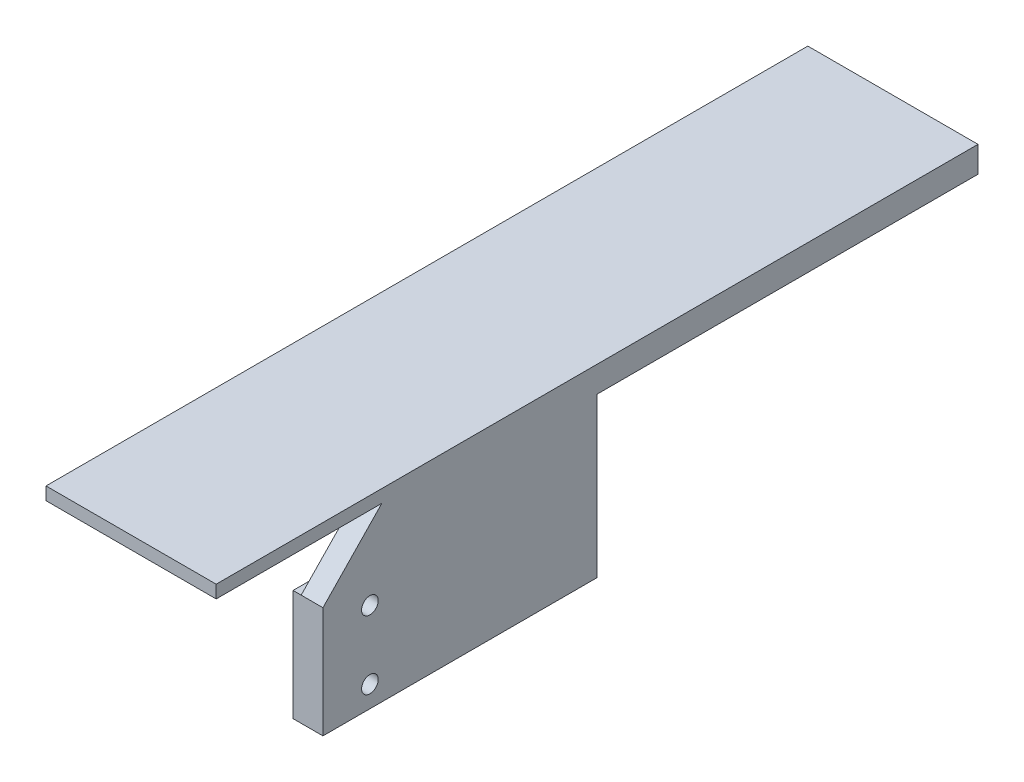
SolidWorks part; units mm, degrees
ref_plane "Front Plane" through (0, 0, 0) normal (0, 0, 1) x (1, 0, 0)
ref_plane "Top Plane" through (0, 0, 0) normal (0, 1, 0) x (1, 0, 0)
ref_plane "Right Plane" through (0, 0, 0) normal (1, 0, 0) x (0, 0, -1)
ref_plane "PY -20.700" through (0, -20.7, 0) normal (0, 1, 0) x (1, 0, 0)
sketch "leg and pad sketch" plane through (0, -20.7, 0) normal (0, 1, 0) x (1, 0, 0)
  line L0 (-0.5513, 30.3327) -> (-0.3673, 30.8194)
  line L1 (-0.3673, 30.8194) -> (-0.028, 31.2139)
  line L2 (-0.028, 31.2139) -> (0.4256, 31.4688)
  line L3 (0.4256, 31.4688) -> (0.939, 31.5534)
  line L4 (0.939, 31.5534) -> (1.4504, 31.4576)
  line L5 (1.4504, 31.4576) -> (1.8983, 31.1928)
  line L6 (1.8983, 31.1928) -> (2.2288, 30.7909)
  line L7 (2.2288, 30.7909) -> (2.4021, 30.3003)
  line L8 (2.4021, 30.3003) -> (2.3973, 29.78)
  line L9 (2.3973, 29.78) -> (2.2152, 29.2926)
  line L10 (2.2152, 29.2926) -> (1.8775, 28.8968)
  line L11 (1.8775, 28.8968) -> (1.4248, 28.6402)
  line L12 (1.4248, 28.6402) -> (0.9118, 28.5536)
  line L13 (0.9118, 28.5536) -> (0.4, 28.6475)
  line L14 (0.4, 28.6475) -> (0.4, -9.98)
  line L15 (0.4, -9.98) -> (1.92, -11.5)
  line L16 (1.92, -11.5) -> (1.92, -31.37)
  line L17 (1.92, -31.37) -> (8.92, -31.37)
  line L18 (8.92, -31.37) -> (8.92, 32.7926)
  line L19 (8.92, 32.7926) -> (-27.2048, 54.5947)
  line L20 (-27.2048, 54.5947) -> (-30.8218, 48.6015)
  line L21 (-30.8218, 48.6015) -> (-0.5513, 30.3327)
extrude "leg and pad" add sketch "leg and pad sketch" along normal mid plane 26
ref_plane "PX 1.350" through (1.35, 0, 0) normal (1, 0, 0) x (0, 0, -1)
sketch "screw head relief sketch" plane through (1.35, 0, 0) normal (1, 0, 0) x (0, 0, -1)
  line L0 (23.4, -12.7) -> (23.4, -6.7)
  line L1 (23.4, -6.7) -> (9.4, -6.7)
  line L2 (9.4, -6.7) -> (9.4, -12.7)
  line L3 (9.4, -12.7) -> (23.4, -12.7)
extrude "screw head relief" cut sketch "screw head relief sketch" against normal mid plane 4.7
sketch "insert flange relief sketch" plane through (0, -20.7, 0) normal (0, 1, 0) x (1, 0, 0)
  line L0 (-18.3249, 39.8914) -> (-17.0331, 42.0318)
  line L1 (-17.0331, 42.0318) -> (-9.7557, 37.6398)
  line L2 (-9.7557, 37.6398) -> (-11.0475, 35.4994)
  line L3 (-11.0475, 35.4994) -> (-18.3249, 39.8914)
revolve "insert flange relief" cut sketch "insert flange relief sketch" angle 360 about L0
sketch "M6 slot end 1 sketch" plane through (0, -20.7, 0) normal (0, 1, 0) x (1, 0, 0)
  line L0 (-20.8933, 41.4415) -> (-16.243, 49.147)
  line L1 (-16.243, 49.147) -> (-13.2464, 47.3385)
  line L2 (-13.2464, 47.3385) -> (-17.8968, 39.633)
  line L3 (-17.8968, 39.633) -> (-20.8933, 41.4415)
revolve "M6 slot end 1" cut sketch "M6 slot end 1 sketch" angle 360 about L0
sketch "M6 slot end 2 sketch" plane through (0, -20.7, 0) normal (0, 1, 0) x (1, 0, 0)
  line L0 (-15.7564, 38.3413) -> (-11.106, 46.0467)
  line L1 (-11.106, 46.0467) -> (-8.1094, 44.2382)
  line L2 (-8.1094, 44.2382) -> (-12.7598, 36.5328)
  line L3 (-12.7598, 36.5328) -> (-15.7564, 38.3413)
revolve "M6 slot end 2" cut sketch "M6 slot end 2 sketch" angle 360 about L0
sketch "M6 slot middle sketch" plane through (0, -20.7, 0) normal (0, 1, 0) x (1, 0, 0)
  line L0 (-15.7564, 38.3413) -> (-20.8933, 41.4415)
  line L1 (-20.8933, 41.4415) -> (-16.243, 49.147)
  line L2 (-16.243, 49.147) -> (-11.106, 46.0467)
  line L3 (-11.106, 46.0467) -> (-15.7564, 38.3413)
extrude "M6 slot middle" cut sketch "M6 slot middle sketch" against normal mid plane 7
ref_plane "PX 5.420" through (5.42, 0, 0) normal (1, 0, 0) x (0, 0, -1)
sketch "screw holes sketch" plane through (5.42, 0, 0) normal (1, 0, 0) x (0, 0, -1)
  circle A0 centre (-20.375, -28.7) radius 1.95
  circle A1 centre (-20.375, -12.7) radius 1.95
extrude "screw holes" cut sketch "screw holes sketch" against normal mid plane 9
ref_plane "PY -2.100" through (0, -2.1, 0) normal (0, 1, 0) x (1, 0, 0)
sketch "foot leg sketch" plane through (0, -2.1, 0) normal (0, 1, 0) x (1, 0, 0)
  line L0 (2.3, 30.0135) -> (2.3, -9.98)
  line L1 (2.3, -9.98) -> (8.92, -9.98)
  line L2 (8.92, -9.98) -> (8.92, 32.7926)
  line L3 (8.92, 32.7926) -> (-27.2048, 54.5947)
  line L4 (-27.2048, 54.5947) -> (-30.2017, 49.6289)
  line L5 (-30.2017, 49.6289) -> (2.3, 30.0135)
extrude "foot leg" add sketch "foot leg sketch" along normal mid plane 12.2
ref_plane "PY 6.535" through (0, 6.535, 0) normal (0, 1, 0) x (1, 0, 0)
sketch "sole under the housing sketch" plane through (0, 6.535, 0) normal (0, 1, 0) x (1, 0, 0)
  line L0 (-30.9218, 122) -> (8.92, 122)
  line L1 (8.92, 122) -> (8.92, -13.03)
  line L2 (8.92, -13.03) -> (-30.9218, -13.03)
  line L3 (-30.9218, -13.03) -> (-30.9218, 122)
extrude "sole under the housing" add sketch "sole under the housing sketch" along normal mid plane 6.07
ref_plane "PY 8.070" through (0, 8.07, 0) normal (0, 1, 0) x (1, 0, 0)
sketch "sole under the block sketch" plane through (0, 8.07, 0) normal (0, 1, 0) x (1, 0, 0)
  line L0 (-30.9218, -12.53) -> (8.92, -12.53)
  line L1 (8.92, -12.53) -> (8.92, -56.37)
  line L2 (8.92, -56.37) -> (-30.9218, -56.37)
  line L3 (-30.9218, -56.37) -> (-30.9218, -12.53)
extrude "sole under the block" add sketch "sole under the block sketch" along normal mid plane 3
ref_plane "PX 6.370" through (6.37, 0, 0) normal (1, 0, 0) x (0, 0, -1)
sketch "seat gusset sketch" plane through (6.37, 0, 0) normal (1, 0, 0) x (0, 0, -1)
  line L0 (-9.48, -8.2) -> (-31.37, -8.2)
  line L1 (-31.37, -8.2) -> (-31.37, -7.7)
  line L2 (-31.37, -7.7) -> (-17.1, 7.07)
  line L3 (-17.1, 7.07) -> (-9.48, 7.07)
  line L4 (-9.48, 7.07) -> (-9.48, -8.2)
extrude "seat gusset" add sketch "seat gusset sketch" along normal mid plane 5.1
ref_plane "PX -19.922" through (-19.9218, 0, 0) normal (1, 0, 0) x (0, 0, -1)
sketch "tail rib sketch" plane through (-19.9218, 0, 0) normal (1, 0, 0) x (0, 0, -1)
  line L0 (53.1, 4) -> (53.1, -12.5)
  line L1 (53.1, -12.5) -> (57.1, -12.5)
  line L2 (57.1, -12.5) -> (120, 3.5)
  line L3 (120, 3.5) -> (120, 4)
  line L4 (120, 4) -> (53.1, 4)
extrude "tail rib" add sketch "tail rib sketch" along normal mid plane 6
sketch "screw head relief to the end sketch" plane through (1.35, 0, 0) normal (1, 0, 0) x (0, 0, -1)
  line L0 (23.4, -12.7) -> (23.4, 3.3)
  line L1 (23.4, 3.3) -> (9.4, 3.3)
  line L2 (9.4, 3.3) -> (9.4, -12.7)
  line L3 (9.4, -12.7) -> (23.4, -12.7)
extrude "screw head relief to the end" cut sketch "screw head relief to the end sketch" against normal mid plane 4.7
equation "\"diffL\" = 608.8mm"
equation "\"diffW\" = 329.4mm"
equation "\"diffT\" = 2.9mm"
equation "\"chanSlotW\" = 12.9mm"
equation "\"chanSlotDepth\" = 11.13mm"
equation "\"chanFloor\" = 1.57mm"
equation "\"chanLeg\" = 12.7mm"
equation "\"lightL\" = 604.8mm"
equation "\"lightW\" = 330.2mm"
equation "\"lightH\" = 92mm"
equation "\"lightSideFlat\" = 30mm"
equation "\"lightSlopeLen\" = 38.9mm"
equation "\"lightWingDepth\" = 50.1mm"
equation "\"lightWingFlat\" = 90.2mm"
equation "\"lightChanW\" = 99.6mm"
equation "\"lightChanStand\" = 44.1mm"
equation "\"insFlangeD\" = 12.3mm"
equation "\"insFromEnd\" = 20.7mm"
equation "\"insUpSlope\" = 20.8mm"
equation "\"gaugeH\" = 10mm"
equation "\"gaugeStepLen\" = 14mm"
equation "\"gaugeStepW0\" = 13.1mm"
equation "\"gaugeStepDW\" = 0.2mm"
equation "\"gaugeSteps\" = 5mm"
equation "\"gaugeHandleLen\" = 30mm"
equation "\"gaugeHandleW\" = 24mm"
equation "\"gaugeSlot0\" = 3mm"
equation "\"gaugeSlotD\" = 0.1mm"
equation "\"gaugeSlotDepth\" = 8mm"
equation "\"gap\" = 25.4mm"
equation "\"edgeL\" = 1mm"
equation "\"edgeW\" = 0.75mm"
equation "\"proud\" = 1.5mm"
equation "\"seatClr\" = 0.15mm"
equation "\"tongueClrZ\" = 0.1mm"
equation "\"tongueClrX\" = 0.25mm"
equation "\"tongueLen\" = 30mm"
equation "\"armSide\" = 45mm"
equation "\"armEnd\" = 20mm"
equation "\"cornerCham\" = 3mm"
equation "\"brkW\" = 26mm"
equation "\"brkT\" = 7mm"
equation "\"brkSeatClr\" = 0.3mm"
equation "\"brkScrewSpan\" = 16mm"
equation "\"pilotD\" = 2.7mm"
equation "\"pilotDepth\" = 10mm"
equation "\"screwClrD\" = 3.9mm"
equation "\"jogBelow\" = 4mm"
equation "\"padT\" = 7mm"
equation "\"padLen\" = 36mm"
equation "\"m6Clr\" = 7mm"
equation "\"m6Slot\" = 6mm"
equation "\"flangeRelD\" = 17mm"
equation "\"flangeRelDepth\" = 1.5mm"
equation "\"relLen\" = 5mm"
equation "\"relDepth\" = 3.3mm"
equation "\"knockN\" = 100mm"
equation "\"petgcfE\" = 3000mm"
equation "\"mockExtent\" = 110mm"
equation "\"relZnear\" = 9.4mm"
equation "\"relZfar\" = 23.4mm"
equation "\"headD\" = 8mm"
equation "\"headH\" = 2.5mm"
equation "\"headFromEnd\" = 6.8mm"
equation "\"headBack\" = 16.4mm"
equation "\"sideClr\" = 0.4mm"
equation "\"cornerRelR\" = 1.5mm"
equation "\"cornerRelBack\" = 0.6mm"
equation "\"endHeadH\" = 2.8mm"
equation "\"footClr\" = 1.2mm"
equation "\"footEndClr\" = 3.5mm"
equation "\"footLift\" = 3.5mm"
equation "\"footBlockClr\" = 0.5mm"
equation "\"footBack\" = 30mm"
equation "\"footFwd\" = 25mm"
equation "\"footRibH\" = 16mm"
equation "\"footRibT\" = 6mm"
